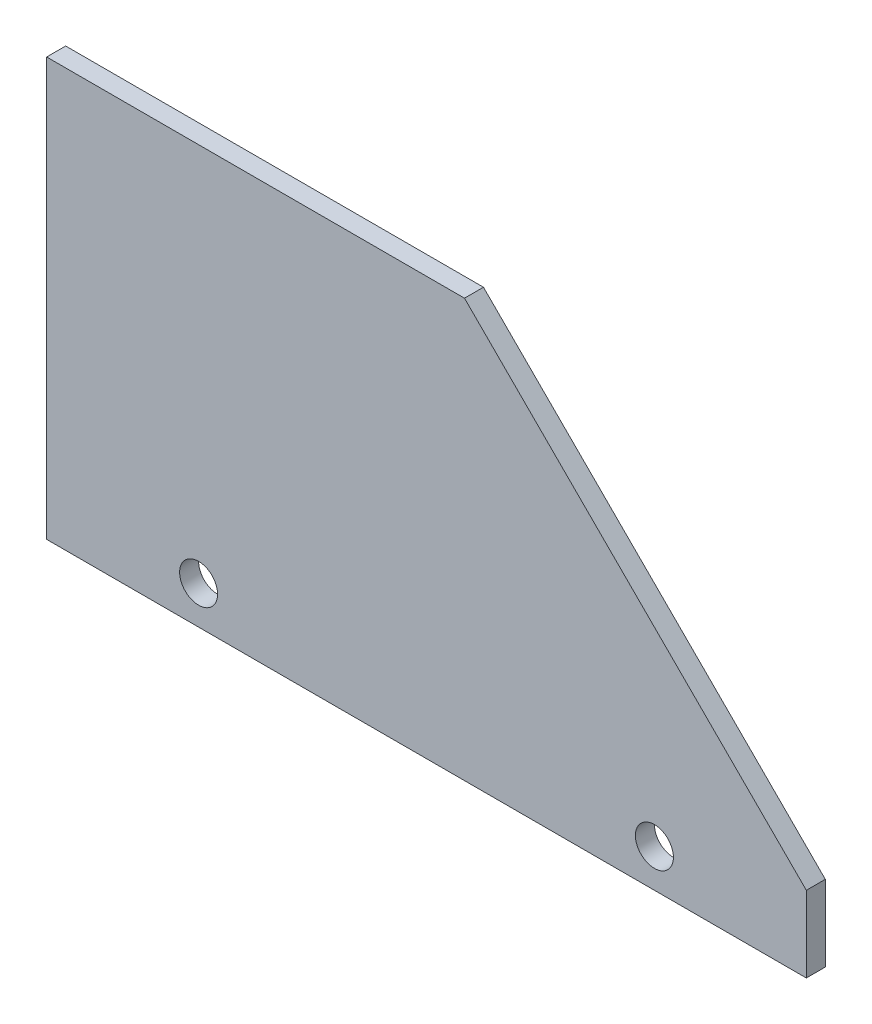
SolidWorks part; units mm, degrees
ref_plane "Front Plane" through (0, 0, 0) normal (0, 0, 1) x (1, 0, 0)
ref_plane "Top Plane" through (0, 0, 0) normal (0, 1, 0) x (1, 0, 0)
ref_plane "Right Plane" through (0, 0, 0) normal (1, 0, 0) x (0, 0, -1)
sketch "Sketch1" plane through (0, 0, 0) normal (0, 0, 1) x (1, 0, 0)
  line L0 (0, 0) -> (0, 34.925)
  line L1 (0, 34.925) -> (34.925, 34.925)
  line L2 (34.925, 34.925) -> (63.5, 6.35)
  line L3 (63.5, 6.35) -> (63.5, 0)
  line L4 (63.5, 0) -> (0, 0)
  dimension "D1" = 6.35
  dimension "D2" = 34.925
  dimension "D3" = 63.5
  dimension "D4" = 135
extrude "Boss-Extrude1" add sketch "Sketch1" along normal blind 1.5875
sketch "Sketch2" plane through (0, 0, 1.5875) normal (0, 0, 1) x (1, 0, 0)
  line L0 (0, 0) -> (63.5, 0) construction
  line L1 (0, 34.925) -> (0, 0) construction
  circle A0 centre (12.7, 3.175) radius 1.5875
  dimension "D1" = 3.175
  dimension "D2" = 3.175
  dimension "D3" = 12.7
extrude "Cut-Extrude1" cut sketch "Sketch2" against normal blind 2.54
pattern_linear "LPattern2" count 2 spacing 38.1 along (1, 0, 0) of "Cut-Extrude1"
